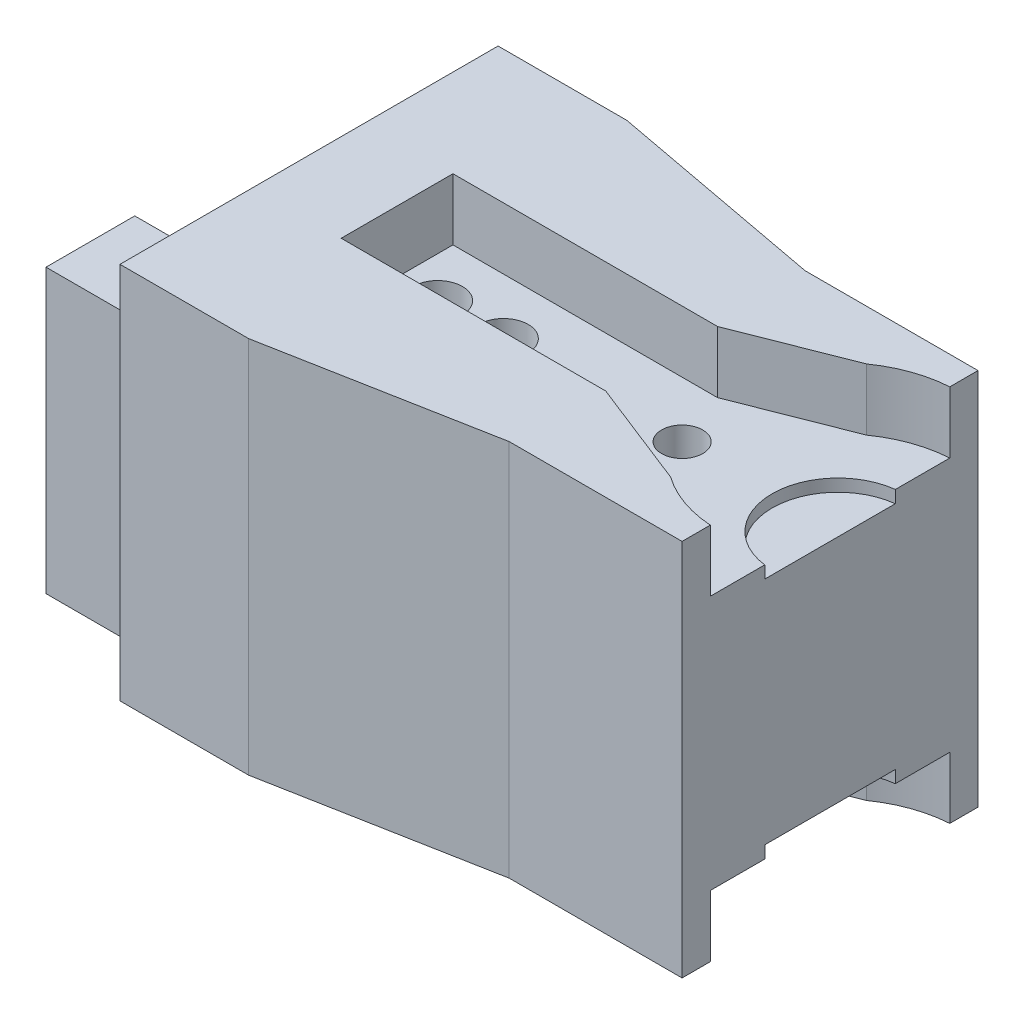
SolidWorks part; units mm, degrees
ref_plane "Front Plane" through (0, 0, 0) normal (0, 0, 1) x (1, 0, 0)
ref_plane "Top Plane" through (0, 0, 0) normal (0, 1, 0) x (1, 0, 0)
ref_plane "Right Plane" through (0, 0, 0) normal (1, 0, 0) x (0, 0, -1)
sketch "Sketch1" plane through (0, 0, 0) normal (0, 1, 0) x (1, 0, 0)
  line L0 (0, 0) -> (14.6038, 0) construction
  line L1 (14.6038, 0) -> (-20.0982, 0) construction
  line L2 (14.6038, -7.2) -> (14.6038, 7.2) construction
  line L3 (-661.2792, -270.937) -> (-113.9458, -270.937) construction
  line L4 (3.082, 5.9567) -> (3.082, -8.253) construction
  line L5 (-17.0385, 7.2) -> (-17.0385, 4.8714) construction
  line L6 (-13.0385, 7.2) -> (-13.0385, 4.8714) construction
  line L7 (6.8243, 9.0002) -> (6.8243, -9.0002)
  line L8 (6.8276, 9.1929) -> (-2.1724, 9.1929) construction
  line L9 (-24.868, 11.5) -> (-24.868, -11.5)
  line L10 (-3.4224, -3.4) -> (-3.4224, 3.4) construction
  line L11 (6.8243, 0.0002) -> (6.8243, 9.0002) construction
  line L12 (6.8243, 0.0002) -> (6.8243, -9.0002) construction
  line L15 (-3.4224, 3.4) -> (3.082, 5.9567)
  line L16 (-3.4224, -3.4) -> (3.082, -5.9567)
  line L17 (-3.4224, 3.4) -> (-19.5134, 3.4)
  line L18 (-19.5134, 3.4) -> (-19.5134, -3.4)
  line L19 (-17.0385, 11.5) -> (-24.868, 11.5)
  line L20 (-19.5134, -3.4) -> (-3.4224, -3.4)
  line L21 (6.8243, 9.0002) -> (-3.6905, 9.0002)
  line L22 (6.8243, -9.0002) -> (-3.6905, -9.0002)
  line L23 (-17.0385, -11.5) -> (-17.0385, 11.5) construction
  line L27 (-3.6905, 9.0002) -> (-17.0385, 11.5)
  line L28 (-3.6905, -9.0002) -> (-17.0385, -11.5)
  line L30 (-24.868, -11.5) -> (-17.0385, -11.5)
  arc A0 (6.8243, 3.9714) -> (6.8243, -3.9714) centre (7.3019, 0) ccw
  circle A1 centre (-17.0385, 0) radius 1.5
  circle A2 centre (-13.0385, 0) radius 1.5
  circle A3 centre (-2.1724, 0) radius 1.25
  arc A4 (6.8243, 7.2844) -> (3.082, 5.9567) centre (7.3019, 0) ccw
  arc A5 (3.082, -5.9567) -> (6.8243, -7.2844) centre (7.3019, 0) ccw
  point P17 (-17.0385, 6.0357)
  point P41 (-3.4224, 0)
  dimension "D4" = 8
  dimension "D5" = 3
  dimension "D7" = 3
  dimension "D10" = 2.5
  dimension "D11" = 14.6
  dimension "D2" = 14.4
  dimension "D3" = 6.8
  dimension "D6" = 4
  dimension "D8" = 9
  dimension "D12" = 9
  dimension "D13" = 3.4
extrude "Boss-Extrude1" add sketch "Sketch1" along normal mid plane 23 contours A5 L16 L20 L18 L17 L15 A4 L7 L21 L27 L19 L9 L30 L28 L22 region at (6.4327, 0, -8.1423)
extrude "Boss-Extrude2" add sketch "Sketch1<13>" along normal mid plane 15.5 contours L16 A5 L7 A0 A4 L15 L17 L18 L20 A3 A2 A1 region at (-4.8753, 0, 0)
sketch "Sketch1<13>" plane through (0, 0, 0) normal (0, 1, 0) x (1, 0, 0) same geometry as "Sketch1"
extrude "Boss-Extrude3" add sketch "Sketch1<14>" along normal mid plane 14 contours L7 A0 region at (5.3434, 0, 0)
sketch "Sketch1<14>" plane through (0, 0, 0) normal (0, 1, 0) x (1, 0, 0) same geometry as "Sketch1"
sketch "Sketch2" plane through (-24.868, 0, 0) normal (-1, 0, 0) x (0, 0, 1)
  line L0 (-11, 0) -> (11, 0) construction
  line L1 (-11.5, -11.5) -> (11.5, -11.5)
  line L2 (-11.5, -11.5) -> (-11.5, 11.5)
  line L3 (-11.5, 11.5) -> (11.5, 11.5)
  line L4 (11.5, -11.5) -> (11.5, 11.5)
  line L5 (0.8, 5.7) -> (0.8, 5.6925)
  line L6 (11, 8.6) -> (11, -8.6)
  line L7 (11, -8.6) -> (5.6, -8.6)
  line L8 (11, 8.6) -> (5.6, 8.6)
  line L9 (5.6, 5.7) -> (5.6, -5.7) construction
  line L10 (5.6, 5.7) -> (0.8, 5.7)
  line L11 (5.6, -5.7) -> (0.8, -5.7)
  line L12 (5.6, 8.6) -> (5.6, 5.7)
  line L13 (5.6, -5.7) -> (5.6, -8.6)
  line L14 (0.8, 5.7) -> (0.8, 5.6925)
  line L15 (0.8, 5.6925) -> (-10.9999, 5.6925)
  line L16 (0.8, -5.6925) -> (-10.9999, -5.6925)
  line L17 (0.8, -5.7) -> (0.8, -5.6925)
  line L18 (-10.9999, 5.6925) -> (-10.9999, -5.6925)
  line L19 (0.8, -5.7) -> (0.8, -5.6925)
  circle A0 centre (-5.3, 0) radius 1.5
  point P11 (0, 0)
  point P19 (5.6, 0)
  dimension "D9" = 3
  dimension "D1" = 11
  dimension "D3" = 8.6
  dimension "D4" = 5.4
  dimension "D5" = 5.7
  dimension "D6" = 4.8
  dimension "D8" = 16.3
extrude "Boss-Extrude4" add sketch "Sketch2" along normal blind 5 contours L15 L18 L16 L17 L11 L13 L7 L6 L8 L12 L10 L14 A0 region at (-24.868, 0, 1.0853)
